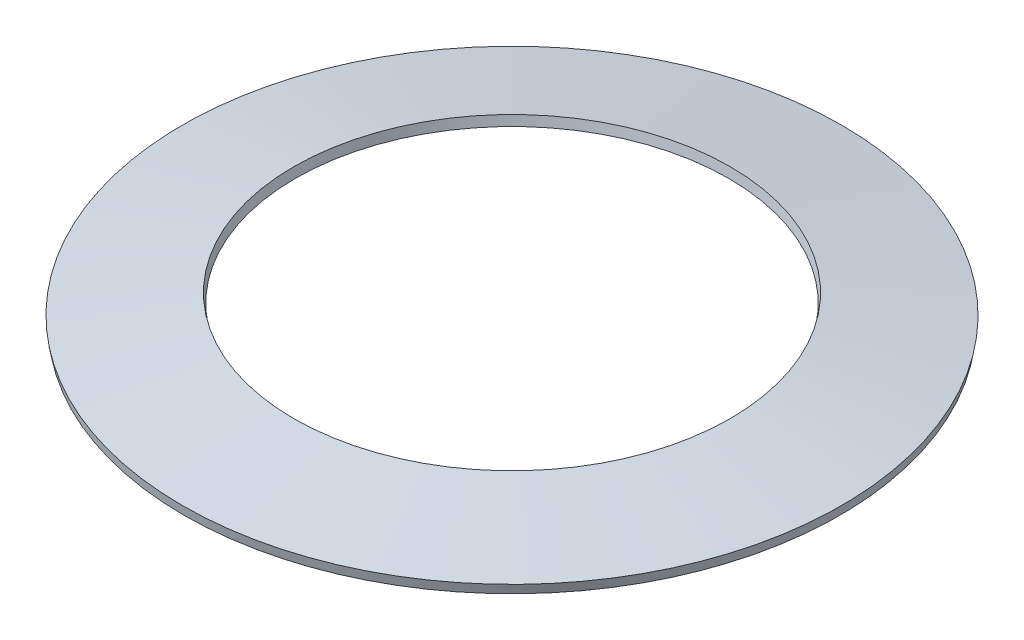
SolidWorks part; units mm, degrees
ref_plane "Plan1" through (0, 0, 0) normal (0, 0, 1) x (1, 0, 0)
ref_plane "Plan2" through (0, 0, 0) normal (0, 1, 0) x (1, 0, 0)
ref_plane "Plan3" through (0, 0, 0) normal (1, 0, 0) x (0, 0, -1)
sketch "Esquisse1" plane through (0, 0, 0) normal (0, 0, 1) x (1, 0, 0)
  line L0 (0, 0) -> (0, 36) construction
  line L1 (-34.8264, 0) -> (-23, 2.0853)
  line L2 (-23, 2.0853) -> (-23.1736, 3.0701)
  line L3 (-23.1736, 3.0701) -> (-35, 0.9848)
  line L4 (-34.8264, 0) -> (-35, 0.9848)
  dimension "D1" = 35
  dimension "D2" = 23
  dimension "D3" = 1
  dimension "D4" = 80
revolve "Base-Révolution" add sketch "Esquisse1" angle 360 about L0
